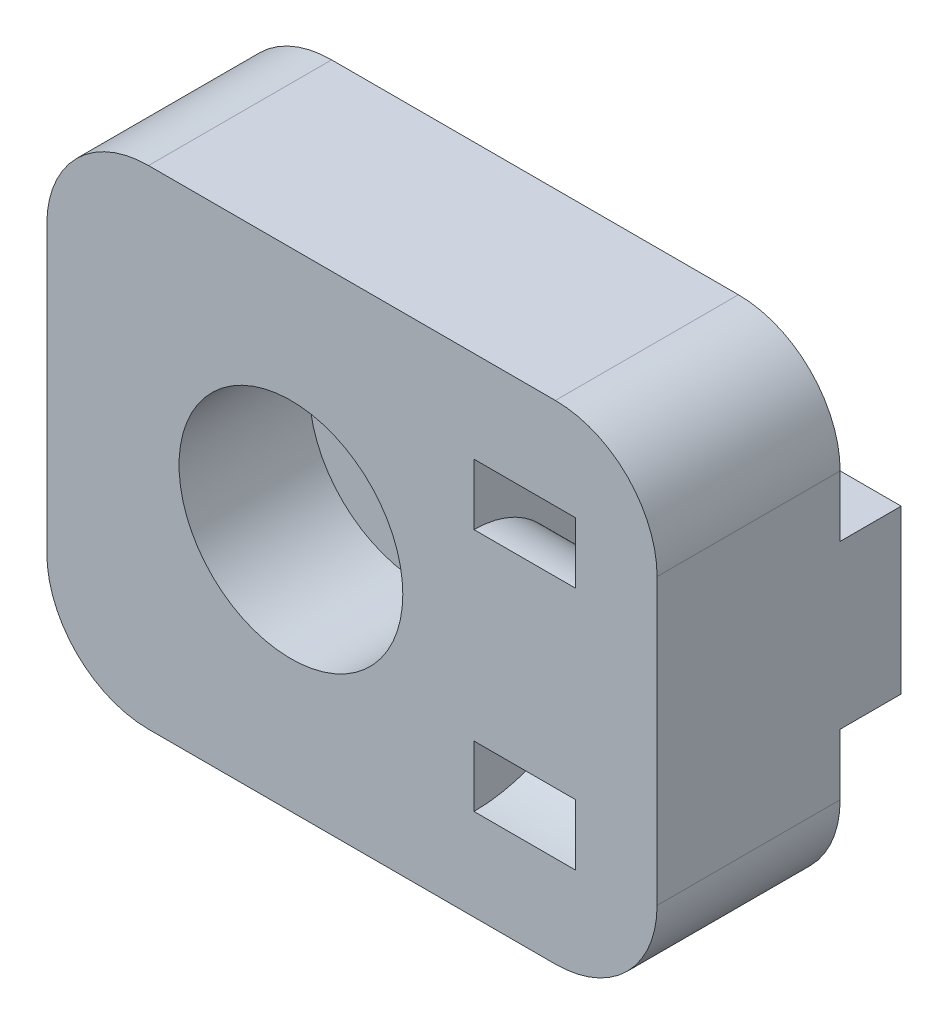
SolidWorks part; units mm, degrees
ref_plane "Přední rovina" through (0, 0, 0) normal (0, 0, 1) x (1, 0, 0)
ref_plane "Horní rovina" through (0, 0, 0) normal (0, 1, 0) x (1, 0, 0)
ref_plane "Pravá rovina" through (0, 0, 0) normal (1, 0, 0) x (0, 0, -1)
sketch "Skica1" plane through (0, 0, 0) normal (0, 0, 1) x (1, 0, 0)
  line L1 (-15, 12) -> (15, 12)
  line L2 (-15, 12) -> (-15, -12)
  line L3 (-15, -12) -> (15, -12)
  line L4 (15, 12) -> (15, -12)
  line L5 (-15, 12) -> (15, -12) construction
  line L6 (-15, -12) -> (15, 12) construction
  point P0 (0, 0)
  dimension "D1" = 24
  dimension "D2" = 30
extrude "Přidat vysunutím1" add sketch "Skica1" along normal blind 9
sketch "Skica2" plane through (0, 0, 9) normal (0, 0, 1) x (1, 0, 0)
  line L0 (-15, 0) -> (15, 0)
  line L1 (-15, 12) -> (-15, -12) construction
  line L2 (15, -12) -> (15, 12) construction
  point P6 (-3, 0)
  dimension "D1" = 12
hole_wizard "Válcové zahloubení pro M6 šrouby s vnitřním šestihranem1" positions "Skica3" profile "Skica4" counterbore size "M6" standard "DIN" end condition through all
sketch "Skica3" plane through (0, 0, 9) normal (0, 0, 1) x (1, 0, 0)
  point P0 (-3, 0)
  point P3 (-24.7725, -8.5167)
sketch "Skica4" plane through (-3, 0, 9) normal (1, 0, 0) x (0, -1, 0)
  line L0 (0, 0) -> (0, 9)
  line L1 (0, 9) -> (3.3, 9)
  line L3 (3.3, 9) -> (3.3, 6.4)
  line L4 (3.3, 6.4) -> (5.5, 6.4)
  line L5 (5.5, 6.4) -> (5.5, 0)
  line L7 (5.5, 0) -> (0, 0)
  line L11 (0, -6.35) -> (0, 107.95) construction
  dimension "Průměr díry skrz" = 6.6
  dimension "Hloubka díry skrz" = 9
  dimension "Průměr válcového zahloubení" = 11
  dimension "Hloubka válcového zahloubení" = 6.4
ref_plane "Rovina1" through (11, 0, 0) normal (1, 0, 0) x (0, 0, -1)
sketch "Tie sketch" plane through (11, 0, 0) normal (1, 0, 0) x (0, 0, -1)
  circle A0 centre (-9, 0) radius 4.5
  circle A1 centre (-9, 0) radius 7.5
  dimension "D1" = 15
  dimension "D2" = 9
extrude "Odebrat vysunutím1" cut sketch "Tie sketch" against normal blind 5
sketch "Skica6" plane through (0, 0, 0) normal (0, 0, -1) x (-1, 0, 0)
  line L0 (0, 12) -> (0, -12)
  line L1 (-15, 12) -> (15, 12) construction
  line L2 (15, -12) -> (-15, -12) construction
  line L3 (15, 12) -> (15, -12) construction
  line L4 (-15, 4) -> (15, 4)
  line L5 (-15, 4) -> (-15, -4)
  line L6 (-15, -4) -> (15, -4)
  line L7 (15, 4) -> (15, -4)
  line L8 (-15, 4) -> (15, -4) construction
  line L9 (-15, -4) -> (15, 4) construction
  circle A0 centre (3, 0) radius 9.5
  point P6 (0, 0)
  line M3 (-15, 12) -> (-15, -12)
  line M5 (15, -12) -> (15, 12)
  dimension "D2" = 19
  dimension "D1" = 8
extrude "Přidat vysunutím2" add sketch "Skica6" along normal blind 3 contours A0 L4 L6 M3 | A0 L6 L4 M5 region at (-13.5934, 0, 0) region at (10.6018, 0, 0)
chamfer "Zkosení1" distance 3 angle 45 1 edges at (6.5, 0, -3)
fillet "Zaoblit1" radius 5 4 edges at (-15, -12, 4.5) (15, -12, 4.5) (15, 12, 4.5) (-15, 12, 4.5)
